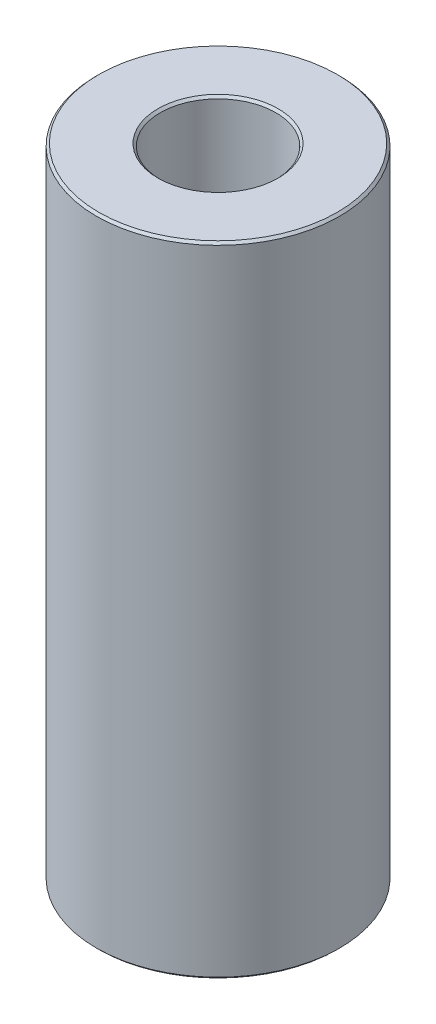
SolidWorks part; units mm, degrees
ref_plane "Front Plane" through (0, 0, 0) normal (0, 0, 1) x (1, 0, 0)
ref_plane "Top Plane" through (0, 0, 0) normal (0, 1, 0) x (1, 0, 0)
ref_plane "Right Plane" through (0, 0, 0) normal (1, 0, 0) x (0, 0, -1)
sketch "Sketch1" plane through (0, 0, 0) normal (0, 1, 0) x (1, 0, 0)
  circle A0 centre (0, 0) radius 42.5
  dimension "SLEEVE_OD" = 85
extrude "Boss-Extrude1" add sketch "Sketch1" along normal blind 223.1406
sketch "Sketch2" plane through (0, 0, 0) normal (0, 1, 0) x (1, 0, 0)
  circle A0 centre (0, 0) radius 20.2136
  dimension "BORE_D" = 40.4271
extrude "Cut-Extrude1" cut sketch "Sketch2" along normal through all
chamfer "Chamfer1" distance 0.8082 angle 45 4 edges at (0, 223.1406, 20.2136) (0, 0, 20.2136) (0, 0, 42.5) (0, 223.1406, 42.5)
